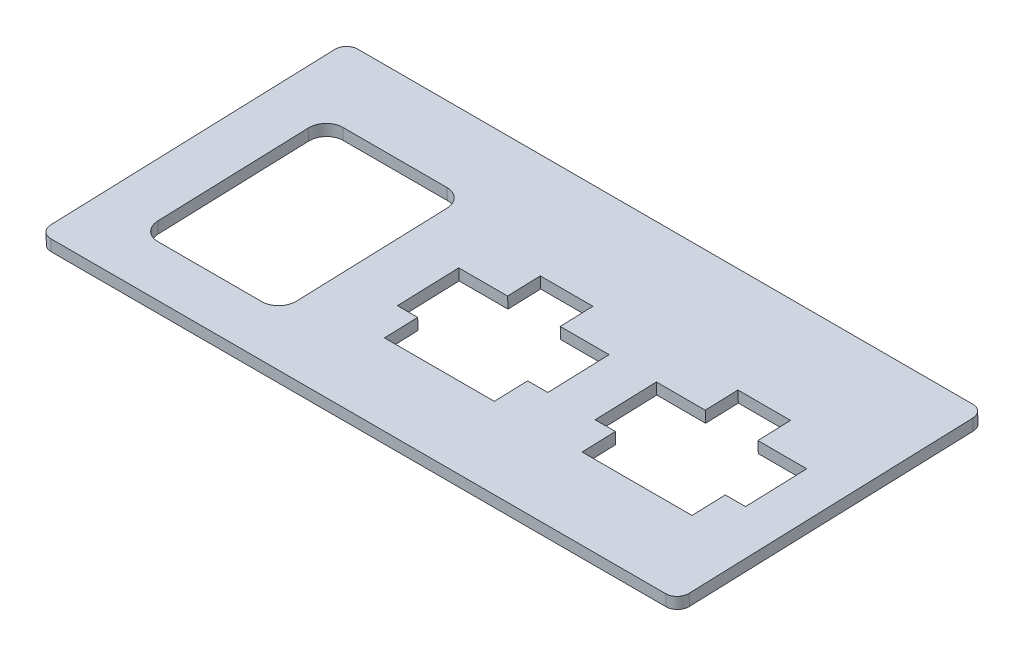
SolidWorks part; units mm, degrees
ref_plane "Front Plane" through (0, 0, 0) normal (0, 0, 1) x (1, 0, 0)
ref_plane "Top Plane" through (0, 0, 0) normal (0, 1, 0) x (1, 0, 0)
ref_plane "Right Plane" through (0, 0, 0) normal (1, 0, 0) x (0, 0, -1)
sketch "Sketch1" plane through (0, -68.9908, -2.4092) normal (0, 0.9994, 0.0349) x (1, 0, 0)
  line L1 (-52.175, -2.8069) -> (-56.175, -2.8069) construction
  line L2 (55.275, 48.7944) -> (-55.275, 48.7944) construction
  line L8 (-55.175, -4.3069) -> (55.175, -4.3069)
  line L9 (55.175, -4.3069) -> (55.175, 48.7944)
  line L10 (55.175, 48.7944) -> (-55.175, 48.7944)
  line L11 (-55.175, 48.7944) -> (-55.175, -4.3069)
  dimension "D1" = 1.5
  dimension "D2" = 3
  dimension "D5" = 3
extrude "Boss-Extrude1" add sketch "Sketch1" along normal blind 2
sketch "Sketch2" plane through (0, -68.9908, -2.4092) normal (0, -0.9994, -0.0349) x (1, 0, 0)
  line L0 (-4.05, -25.5688) -> (-4.05, -31.2188)
  line L1 (-43.175, -4.2188) -> (-25.175, -4.2188)
  line L2 (-46.175, -7.2188) -> (-46.175, -33.2188)
  line L3 (-43.175, -36.2188) -> (-25.175, -36.2188)
  line L4 (-22.175, -7.2188) -> (-22.175, -33.2188)
  line L5 (-12.5, -14.9688) -> (-9, -14.9688)
  line L6 (-12.5, -14.9688) -> (-12.5, -25.5688)
  line L7 (-12.5, -25.5688) -> (-4.05, -25.5688)
  line L8 (13.5, -14.9688) -> (13.5, -25.5688)
  line L9 (-9, -9.2188) -> (10, -9.2188)
  line L10 (-9, -9.2188) -> (-9, -14.9688)
  line L11 (-4.05, -31.2188) -> (5.05, -31.2188)
  line L12 (10, -9.2188) -> (10, -14.9688)
  line L13 (10, -14.9688) -> (13.5, -14.9688)
  line L14 (5.05, -25.5688) -> (5.05, -31.2188)
  line L15 (5.05, -25.5688) -> (13.5, -25.5688)
  line L16 (-13, -6.7188) -> (14, -33.7188) construction
  line L17 (-13, -6.7188) -> (14, -6.7188) construction
  line L18 (-13, -6.7188) -> (-13, -33.7188) construction
  line L19 (-13, -33.7188) -> (14, -33.7188) construction
  line L20 (14, -6.7188) -> (14, -33.7188) construction
  line L21 (17.5875, 3.7502) -> (17.5875, -36.664) construction
  line L22 (47.675, -20.2688) -> (21.675, -20.2688) construction
  line L23 (34.675, -9.2188) -> (34.675, -31.2188) construction
  line L24 (21.175, -6.7188) -> (21.175, -33.7188) construction
  line L25 (48.175, -33.7188) -> (21.175, -33.7188) construction
  line L26 (48.175, -6.7188) -> (48.175, -33.7188) construction
  line L27 (48.175, -6.7188) -> (21.175, -6.7188) construction
  line L28 (-48.175, -20.2188) -> (-46.175, -20.2188) construction
  line L29 (-48.175, -2.2188) -> (-20.175, -2.2188) construction
  line L30 (-48.175, -2.2188) -> (-48.175, -38.2188) construction
  line L31 (-48.175, -38.2188) -> (-20.175, -38.2188) construction
  line L32 (-20.175, -2.2188) -> (-20.175, -38.2188) construction
  line L33 (-34.175, -4.2188) -> (-34.175, -2.2188) construction
  line L34 (0.5, -9.2188) -> (0.5, -31.2188) construction
  line L35 (-12.5, -20.2688) -> (13.5, -20.2688) construction
  line L36 (48.175, -6.7188) -> (21.175, -33.7188) construction
  line L37 (30.125, -25.5688) -> (21.675, -25.5688)
  line L38 (30.125, -25.5688) -> (30.125, -31.2188)
  line L39 (25.175, -14.9688) -> (21.675, -14.9688)
  line L40 (25.175, -9.2188) -> (25.175, -14.9688)
  line L41 (39.225, -31.2188) -> (30.125, -31.2188)
  line L42 (44.175, -9.2188) -> (44.175, -14.9688)
  line L43 (44.175, -9.2188) -> (25.175, -9.2188)
  line L44 (21.675, -14.9688) -> (21.675, -25.5688)
  line L45 (47.675, -25.5688) -> (39.225, -25.5688)
  line L46 (47.675, -14.9688) -> (47.675, -25.5688)
  line L47 (47.675, -14.9688) -> (44.175, -14.9688)
  line L48 (39.225, -25.5688) -> (39.225, -31.2188)
  line L49 (21.175, -20.2188) -> (14, -20.2188) construction
  line L50 (-55.175, 4.3069) -> (55.175, 4.3069) construction
  line L51 (48.175, -20.2188) -> (52.175, -20.2188) construction
  line L52 (55.175, 4.3069) -> (55.175, -48.7944) construction
  line L53 (-46.6517, -44.7445) -> (46.6517, -44.7445) construction
  line L54 (-13, -20.2188) -> (-20.175, -20.2188) construction
  line L55 (-34.175, -2.2188) -> (-34.175, 4.3069) construction
  line L56 (-34.175, -38.2188) -> (-34.175, -44.7445) construction
  line L57 (-55.175, -48.7944) -> (-55.175, 4.3069) construction
  line L58 (-48.175, -20.2188) -> (-52.175, -20.2188) construction
  arc A0 (-46.175, -33.2188) -> (-43.175, -36.2188) centre (-43.175, -33.2188) ccw
  arc A1 (-25.175, -36.2188) -> (-22.175, -33.2188) centre (-25.175, -33.2188) ccw
  arc A2 (-25.175, -4.2188) -> (-22.175, -7.2188) centre (-25.175, -7.2188) cw
  arc A3 (-43.175, -4.2188) -> (-46.175, -7.2188) centre (-43.175, -7.2188) ccw
  point P28 (0.5, -20.2188)
  point P63 (34.675, -20.2188)
  dimension "D1" = 3
  dimension "D2" = 32
  dimension "D3" = 24
  dimension "D4" = 28
  dimension "D5" = 36
  dimension "D6" = 26
  dimension "D7" = 22
  dimension "D8" = 10.6
  dimension "D9" = 19
  dimension "D10" = 9.1
  dimension "D11" = 5.75
  dimension "D12" = 27
  dimension "D13" = 27
  dimension "D14" = 4
  dimension "D15" = 3
  dimension "D16" = 3
extrude "Cut-Extrude1" cut sketch "Sketch2" against normal up to next
fillet "Fillet1" radius 2 4 edges at (-55.175, -68.1418, 1.93) (55.175, -68.1418, 1.93) (55.175, -66.2886, -51.139) (-55.175, -66.2886, -51.139)
